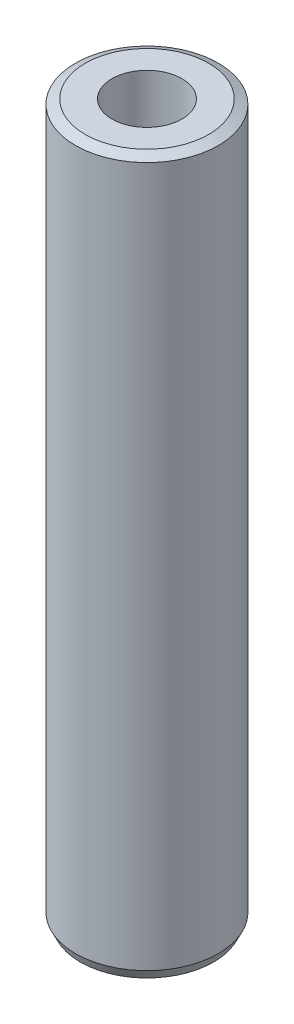
SolidWorks part; units mm, degrees
ref_plane "Front Plane" through (0, 0, 0) normal (0, 0, 1) x (1, 0, 0)
ref_plane "Top Plane" through (0, 0, 0) normal (0, 1, 0) x (1, 0, 0)
ref_plane "Right Plane" through (0, 0, 0) normal (1, 0, 0) x (0, 0, -1)
sketch "Sketch1" plane through (0, 0, 0) normal (0, 1, 0) x (1, 0, 0)
  circle A0 centre (0, 0) radius 60
  dimension "SHAFT_OD" = 120
extrude "Boss-Extrude1" add sketch "Sketch1" along normal blind 600
sketch "Sketch2" plane through (0, 0, 0) normal (0, 1, 0) x (1, 0, 0)
  circle A0 centre (0, 0) radius 29.4147
  dimension "BORE_D" = 58.8294
extrude "Cut-Extrude1" cut sketch "Sketch2" along normal through all
chamfer "Chamfer1" distance 3.9628 angle 64.049 2 edges at (0, 600, 60) (0, 0, 60) first distance on face at (0, 600, 60) first distance on face at (0, 0, 29.4147)
